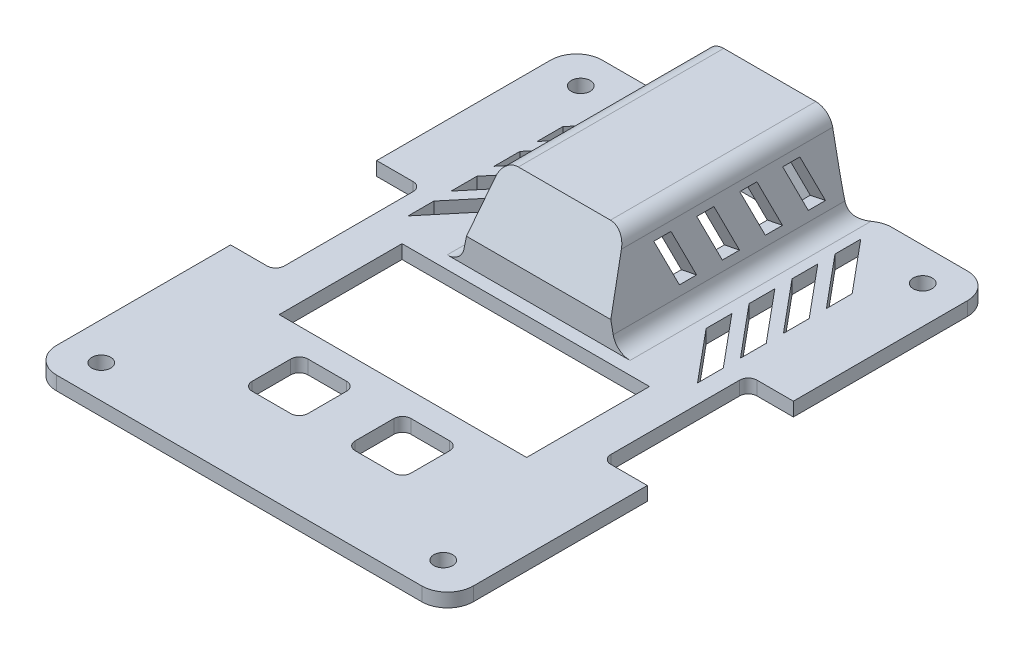
SolidWorks part; units mm, degrees
ref_plane "前视基准面" through (0, 0, 0) normal (0, 0, 1) x (1, 0, 0)
ref_plane "上视基准面" through (0, 0, 0) normal (0, 1, 0) x (1, 0, 0)
ref_plane "右视基准面" through (0, 0, 0) normal (1, 0, 0) x (0, 0, -1)
sketch "草图1" plane through (0, 0, 0) normal (0, 1, 0) x (1, 0, 0)
  line L0 (-24.25, 8.5) -> (-19, 8.5)
  line L1 (-21.25, -31.75) -> (21.25, -31.75)
  line L2 (-24.25, -28.75) -> (-24.25, -8.5)
  line L3 (-21.25, 31.75) -> (21.25, 31.75)
  line L4 (24.25, -28.75) -> (24.25, -8.5)
  line L5 (-24.25, -31.75) -> (24.25, 31.75) construction
  line L6 (-24.25, 31.75) -> (24.25, -31.75) construction
  line L7 (-19, 8.5) -> (-19, -8.5)
  line L8 (-19, -8.5) -> (-24.25, -8.5)
  line L9 (0, -55) -> (0, 55) construction
  line L10 (19, -8.5) -> (24.25, -8.5)
  line L11 (19, 8.5) -> (19, -8.5)
  line L12 (24.25, 8.5) -> (19, 8.5)
  line L13 (-24.25, 8.5) -> (-24.25, 28.75)
  line L14 (24.25, 8.5) -> (24.25, 28.75)
  arc A0 (-24.25, -28.75) -> (-21.25, -31.75) centre (-21.25, -28.75) ccw
  arc A1 (21.25, -31.75) -> (24.25, -28.75) centre (21.25, -28.75) ccw
  arc A2 (24.25, 28.75) -> (21.25, 31.75) centre (21.25, 28.75) ccw
  arc A3 (-21.25, 31.75) -> (-24.25, 28.75) centre (-21.25, 28.75) ccw
  point P0 (0, 0)
  point P20 (-19, 0)
  dimension "D3" = 3
  dimension "D1" = 48.5
  dimension "D2" = 63.5
  dimension "D4" = 5.25
  dimension "D5" = 17
extrude "凸台-拉伸1" add sketch "草图1" along normal blind 1.6 contours L3 A2 L14 L12 L11 L10 L4 A1 L1 A0 L2 L8 L7 L0 L13 A3
sketch "草图2" plane through (0, 1.6, 0) normal (0, 1, 0) x (1, 0, 0)
  line L0 (0, -0.88) -> (0, 0.88) construction
  line L1 (-0.88, 0) -> (0.88, 0) construction
  circle A0 centre (-19.9, 27.9) radius 1.1
  circle A1 centre (19.9, 27.9) radius 1.1
  circle A2 centre (19.9, -27.9) radius 1.1
  circle A3 centre (-19.9, -27.9) radius 1.1
  dimension "D1" = 2.2
  dimension "D2" = 39.8
  dimension "D3" = 55.8
extrude "切除-拉伸1" cut sketch "草图2" against normal through all
fillet "圆角1" radius 1 4 edges at (19, 0.8, 8.5) (19, 0.8, -8.5) (-19, 0.8, 8.5) (-19, 0.8, -8.5)
sketch "草图4" plane through (0, 1.6, 0) normal (0, 1, 0) x (1, 0, 0)
  line L0 (-21.25, -31.75) -> (21.25, -31.75) construction
  line L1 (-9.25, -22) -> (-2.75, -22)
  line L2 (-9.25, -22) -> (-9.25, -15.5)
  line L3 (-9.25, -15.5) -> (-2.75, -15.5)
  line L4 (-2.75, -22) -> (-2.75, -15.5)
  line L5 (-24.25, -28.75) -> (-24.25, -8.5) construction
  line L6 (0, -0.88) -> (0, 0.88) construction
  line L7 (9.25, -15.5) -> (2.75, -15.5)
  line L8 (2.75, -22) -> (2.75, -15.5)
  line L9 (9.25, -22) -> (2.75, -22)
  line L10 (9.25, -22) -> (9.25, -15.5)
  dimension "D1" = 16.25
  dimension "D2" = 9.75
  dimension "D3" = 15
  dimension "D4" = 21.5
extrude "切除-拉伸2" cut sketch "草图4" against normal through all
fillet "圆角2" radius 1 8 edges at (-9.25, 0.8, 22) (-2.75, 0.8, 22) (-9.25, 0.8, 15.5) (-2.75, 0.8, 15.5) (9.25, 0.8, 22) (2.75, 0.8, 22) (2.75, 0.8, 15.5) (9.25, 0.8, 15.5)
sketch "草图8" plane through (0, 1.6, 0) normal (0, 1, 0) x (1, 0, 0)
  line L0 (14.4, 1.6) -> (-14.4, 1.6)
  line L1 (-14.4, 1.6) -> (-14.4, -12.7)
  line L2 (-14.4, -12.7) -> (14.4, -12.7)
  line L3 (14.4, -12.7) -> (14.4, 1.6)
  line L4 (-14, 1.2) -> (-14, -12.3)
  line L5 (-14, -12.3) -> (14, -12.3)
  line L6 (14, -12.3) -> (14, 1.2)
  line L7 (14, 1.2) -> (-14, 1.2)
  line L8 (-14, 1.2) -> (-14, -12.3) construction
  line L9 (-14, -12.3) -> (14, -12.3) construction
  line L10 (14, -12.3) -> (14, 1.2) construction
  line L11 (14, 1.2) -> (-14, 1.2) construction
  dimension "D1" = 0
  dimension "D2" = 0.4
extrude "切除-拉伸3" cut sketch "草图8" against normal up to surface (1.6 mm away) up to face at (-6, 0, 18.75)
sketch "草图10" plane through (0, 0, -31.75) normal (0, 0, -1) x (-1, 0, 0)
  line L0 (-9, 1.6) -> (9, 1.6)
  line L1 (21.25, 1.6) -> (-21.25, 1.6) construction
  line L2 (-9, 1.6) -> (-7, 11.6)
  line L3 (-7, 11.6) -> (7, 11.6)
  line L4 (7, 11.6) -> (9, 1.6)
  point P4 (0, 1.6)
  point P5 (0, 11.6)
  dimension "D1" = 18
  dimension "D2" = 14
  dimension "D3" = 10
extrude "凸台-拉伸2" add sketch "草图10" against normal offset from surface (26.9 mm away) 1.5 from offset 1.75 up to face at (0, 0.8, -1.6) offset against normal yes
sketch "草图11" plane through (0, 0, 0) normal (1, 0, 0) x (0, 0, -1)
  line L0 (6.1, 11.6) -> (3.1, 4.6)
  line L1 (3.1, 11.6) -> (30, 11.6) construction
  line L2 (3.1, 1.6) -> (3.1, 11.6) construction
  line L3 (3.1, 4.6) -> (3.1, 11.6)
  line L4 (3.1, 11.6) -> (6.1, 11.6)
  dimension "D1" = 3
  dimension "D2" = 3
extrude "切除-拉伸4" cut sketch "草图11" against normal through all both and the other way through all
sketch "草图14" plane through (0, 1.6, 0) normal (0, 1, 0) x (1, 0, 0)
  line L7 (9, 30) -> (11.5, 31.75)
  line L8 (-21.25, 31.75) -> (21.25, 31.75) construction
  line L9 (11.5, 31.75) -> (-11.5, 31.75)
  line L10 (-11.5, 31.75) -> (-9, 30)
  point P8 (0, 29.75)
  point P9 (0, 31.75)
  line M48 (21.25, 31.75) -> (-21.25, 31.75)
  line M50 (-9, 30) -> (9, 30)
  dimension "D1" = 23
extrude "切除-拉伸6" cut sketch "草图14" against normal through all contours L10 L7 M48 M50 region at (0, 1.6, -30.9106)
shell "抽壳3" thickness 1.8 removed face at (0, 0, 5.55)
fillet "圆角3" radius 3 4 edges at (-11.5, 0.8, -31.75) (-9, 0.8, -30) (11.5, 0.8, -31.75) (9, 0.8, -30) tangent propagation no
sketch "草图15" plane through (0, 0, -30) normal (0, 0, -1) x (-1, 0, 0)
  line L0 (21.25, 1.6) -> (12.4457, 1.6) construction
  circle A0 centre (0, 5.1) radius 3.1
  dimension "D1" = 6.2
  dimension "D2" = 3.5
extrude "切除-拉伸8" cut sketch "草图15" against normal up to surface (1.8 mm away) contours A0 up to face at (0, 4.9, -28.2)
fillet "圆角5" radius 2 4 edges at (9, 1.6, -16.6265) (-9, 1.6, -16.6265) (7, 11.6, -18.05) (-7, 11.6, -18.05)
sketch "草图16" plane through (0, 1.6, 0) normal (0, 1, 0) x (1, 0, 0)
  line L0 (-11.8396, 25.75) -> (-11.8396, 28.75)
  line L1 (-11.8396, 25.75) -> (-16.8396, 19.75)
  line L2 (-11.8396, 28.75) -> (-16.8396, 22.75)
  line L3 (-16.8396, 19.75) -> (-16.8396, 22.75)
  line L4 (-10.6396, 3.1) -> (-10.6396, 31.1477) construction
  line L5 (-21.25, 31.75) -> (-12.4457, 31.75) construction
  line L14 (-11.8396, 20.75) -> (-11.8396, 23.75)
  line L15 (-11.8396, 20.75) -> (-16.8396, 14.75)
  line L16 (-16.8396, 14.75) -> (-16.8396, 17.75)
  line L17 (-11.8396, 23.75) -> (-16.8396, 17.75)
  line L18 (-11.8396, 15.75) -> (-11.8396, 18.75)
  line L19 (-11.8396, 15.75) -> (-16.8396, 9.75)
  line L20 (-16.8396, 9.75) -> (-16.8396, 12.75)
  line L21 (-11.8396, 18.75) -> (-16.8396, 12.75)
  line L22 (-11.8396, 10.75) -> (-11.8396, 13.75)
  line L23 (-11.8396, 10.75) -> (-16.8396, 4.75)
  line L24 (-16.8396, 4.75) -> (-16.8396, 7.75)
  line L25 (-11.8396, 13.75) -> (-16.8396, 7.75)
  dimension "D1" = 5
  dimension "D2" = 3
  dimension "D3" = 6
  dimension "D4" = 1.2
  dimension "D5" = 3
  dimension "D7" = 5
  dimension "D6" = 4
extrude "切除-拉伸9" cut sketch "草图16" against normal through all
mirror "镜向1" about plane through (0, 0, 0) normal (1, 0, 0) of "切除-拉伸9"
sketch "草图18" plane through (-8.9615, 1.7923, 0) normal (-0.9806, 0.1961, 0) x (0, 0, 1)
  line L0 (-28, 2.4435) -> (-26, 2.4435)
  line L1 (-28, 2.4435) -> (-26, 7.4435)
  line L2 (-26, 2.4435) -> (-24, 7.4435)
  line L3 (-26, 7.4435) -> (-24, 7.4435)
  line L4 (-30.0656, 1.4435) -> (-3.1, 1.4435) construction
  line L5 (-30, 8.101) -> (-30, 1.901) construction
  line L6 (-23, 2.4435) -> (-21, 2.4435)
  line L7 (-23, 2.4435) -> (-21, 7.4435)
  line L8 (-21, 7.4435) -> (-19, 7.4435)
  line L9 (-21, 2.4435) -> (-19, 7.4435)
  line L10 (-18, 2.4435) -> (-16, 2.4435)
  line L11 (-18, 2.4435) -> (-16, 7.4435)
  line L12 (-16, 7.4435) -> (-14, 7.4435)
  line L13 (-16, 2.4435) -> (-14, 7.4435)
  line L14 (-13, 2.4435) -> (-11, 2.4435)
  line L15 (-13, 2.4435) -> (-11, 7.4435)
  line L16 (-11, 7.4435) -> (-9, 7.4435)
  line L17 (-11, 2.4435) -> (-9, 7.4435)
  dimension "D1" = 2
  dimension "D2" = 5
  dimension "D3" = 1
  dimension "D4" = 2
  dimension "D5" = 2
  dimension "D7" = 5
  dimension "D6" = 4
extrude "切除-拉伸10" cut sketch "草图18" against normal up to surface (1.8 mm away) up to face at (-6.5311, 4.7661, -14.6974)
mirror "镜向2" about plane through (0, 0, 0) normal (1, 0, 0) of "切除-拉伸10"
